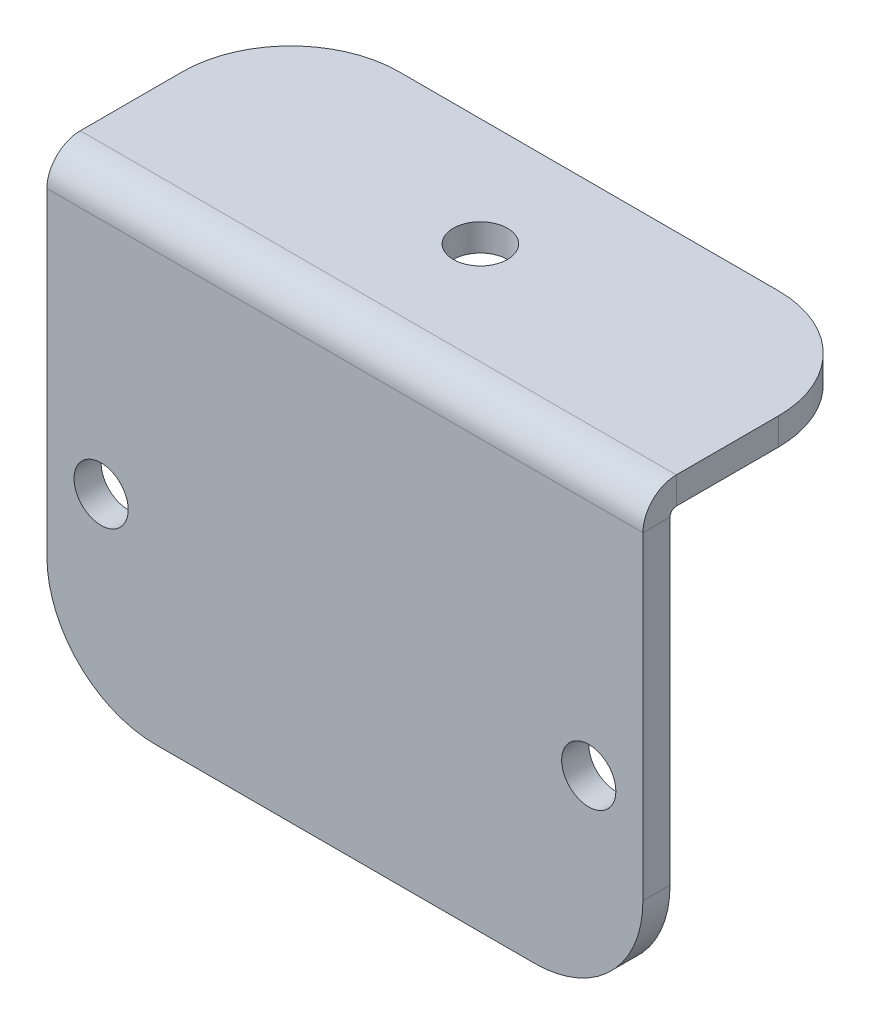
SolidWorks part; units mm, degrees
note: The reader was unsure of these and kept them because the rebuilt part matched: bend radius of "BaseBend1".
material "6061-T6 (SS)"
ref_plane "Front Plane" through (0, 0, 0) normal (0, 0, 1) x (1, 0, 0)
ref_plane "Top Plane" through (0, 0, 0) normal (0, 1, 0) x (1, 0, 0)
ref_plane "Right Plane" through (0, 0, 0) normal (1, 0, 0) x (0, 0, -1)
sketch "Sketch1" plane through (0, 0, 0) normal (1, 0, 0) x (0, 0, -1)
  line L0 (25.4, 0) -> (0, 0)
  line L1 (0, 0) -> (0, -50.8)
  dimension "D1" = 25.4
  dimension "D2" = 50.8
base flange "Base-Flange1" sketch "Sketch1" end condition mid plane depth 69.85 reverse direction no thickness 3.175 reverse thickness direction no bend radius 0.7366
bend "BaseBend1" bend radius 0.7366 bend angle 90 parameters "D5"=1
sketch "Sketch6" plane through (0, 0, 3.175) normal (0, 0, 1) x (1, 0, 0)
  line L0 (-28.575, -28.575) -> (28.575, -28.575) construction
  line L1 (34.925, -50.8) -> (-34.925, -50.8) construction
  circle A0 centre (-28.575, -28.575) radius 3.175
  circle A1 centre (28.575, -28.575) radius 3.175
  point P4 (0, -28.575)
  dimension "D2" = 6.35
  dimension "D1" = 57.15
  dimension "D3" = 22.225
extrude "Cut-Extrude1" cut sketch "Sketch6" against normal through all normal cut yes
fillet "Fillet1" radius 12.7 4 edges at (34.925, -50.8, 1.5875) (-34.925, -50.8, 1.5875) (34.925, 1.5875, -25.4) (-34.925, 1.5875, -25.4)
sketch "Sketch7" plane through (0, 3.175, 0) normal (0, 1, 0) x (1, 0, 0)
  line L0 (22.225, 25.4) -> (-22.225, 25.4) construction
  circle A0 centre (0, 12.7) radius 3.175
  point P2 (0, 0)
  dimension "D1" = 6.35
  dimension "D2" = 12.7
extrude "Cut-Extrude2" cut sketch "Sketch7" against normal through all normal cut yes
sketch "Bend-Lines1" [suppressed] plane through (0, 0, 0) normal (0, 1, 0) x (1, 0, 0)
sketch "Bounding-Box1" [suppressed] plane through (0, 0, 0) normal (0, 1, 0) x (1, 0, 0)
sheet metal parameters "Sheet-Metal1" thickness 3.175 parameters "D1"=0.7366
flat pattern "Flat-Pattern1" [suppressed]
sketch "Bend-Lines2" plane through (0, 0, 0) normal (0, 0, -1) x (-1, 0, 0)
  line L0 (-63.5, 1.0887) -> (63.5, 1.0887) construction
  line L1 (-63.5, 1.0887) -> (63.5, 1.0887) construction
sketch3d "Bounding-Box2" [suppressed]
  line L0 (0, -50.8, 0) -> (127, -50.8, 0) construction
  line L1 (0, 27.5775, 0) -> (127, 27.5775, 0) construction
  line L2 (0, -50.8, 0) -> (0, 27.5775, 0) construction
  line L3 (127, -50.8, 0) -> (127, 27.5775, 0) construction
bend of the flat pattern "Flatten-<BaseBend1>1"
sheet metal parameters "Sheet-Metal2" thickness 3.175 parameters "D1"=0.7366
flat pattern "Flat-Pattern1"
sketch "Bend-Lines2" plane through (0, 0, 0) normal (0, 0, -1) x (-1, 0, 0)
  line L0 (-34.925, 1.0887) -> (34.925, 1.0887) construction
  line L1 (-34.925, 1.0887) -> (34.925, 1.0887) construction
sketch3d "Bounding-Box2" [suppressed]
  line L0 (0, 27.5775, 0) -> (0, -50.8, 0) construction
  line L1 (69.85, 27.5775, 0) -> (69.85, -50.8, 0) construction
  line L2 (0, 27.5775, 0) -> (69.85, 27.5775, 0) construction
  line L3 (0, -50.8, 0) -> (69.85, -50.8, 0) construction
bend of the flat pattern "Flatten-<BaseBend1>1"
sheet metal parameters "Sheet-Metal3" thickness 3.175 parameters "D1"=0.7366
flat pattern "Flat-Pattern1"
sketch "Bend-Lines2" plane through (0, 0, 0) normal (0, 0, -1) x (-1, 0, 0)
  line L0 (-34.925, 1.0887) -> (34.925, 1.0887) construction
  line L1 (-34.925, 1.0887) -> (34.925, 1.0887) construction
sketch3d "Bounding-Box2" [suppressed]
  line L0 (0, 27.5775, 0) -> (0, -50.8, 0) construction
  line L1 (69.85, 27.5775, 0) -> (69.85, -50.8, 0) construction
  line L2 (0, 27.5775, 0) -> (69.85, 27.5775, 0) construction
  line L3 (0, -50.8, 0) -> (69.85, -50.8, 0) construction
bend of the flat pattern "Flatten-<BaseBend1>1"
